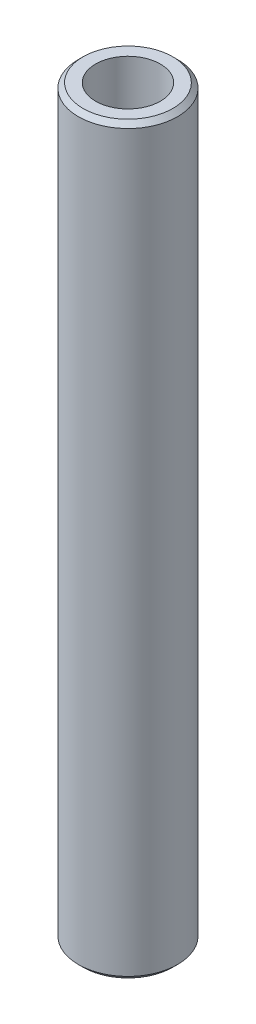
SolidWorks part; units mm, degrees
ref_plane "Front Plane" through (0, 0, 0) normal (0, 0, 1) x (1, 0, 0)
ref_plane "Top Plane" through (0, 0, 0) normal (0, 1, 0) x (1, 0, 0)
ref_plane "Right Plane" through (0, 0, 0) normal (1, 0, 0) x (0, 0, -1)
sketch "Sketch1" plane through (0, 0, 0) normal (0, 1, 0) x (1, 0, 0)
  circle A0 centre (0, 0) radius 40
  dimension "SHAFT_OD" = 80
extrude "Boss-Extrude1" add sketch "Sketch1" along normal blind 600
sketch "Sketch2" plane through (0, 0, 0) normal (0, 1, 0) x (1, 0, 0)
  circle A0 centre (0, 0) radius 26.0804
  dimension "BORE_D" = 52.1609
extrude "Cut-Extrude1" cut sketch "Sketch2" along normal through all
chamfer "Chamfer1" distance 3.8213 angle 45 2 edges at (0, 600, 40) (0, 0, 40)
